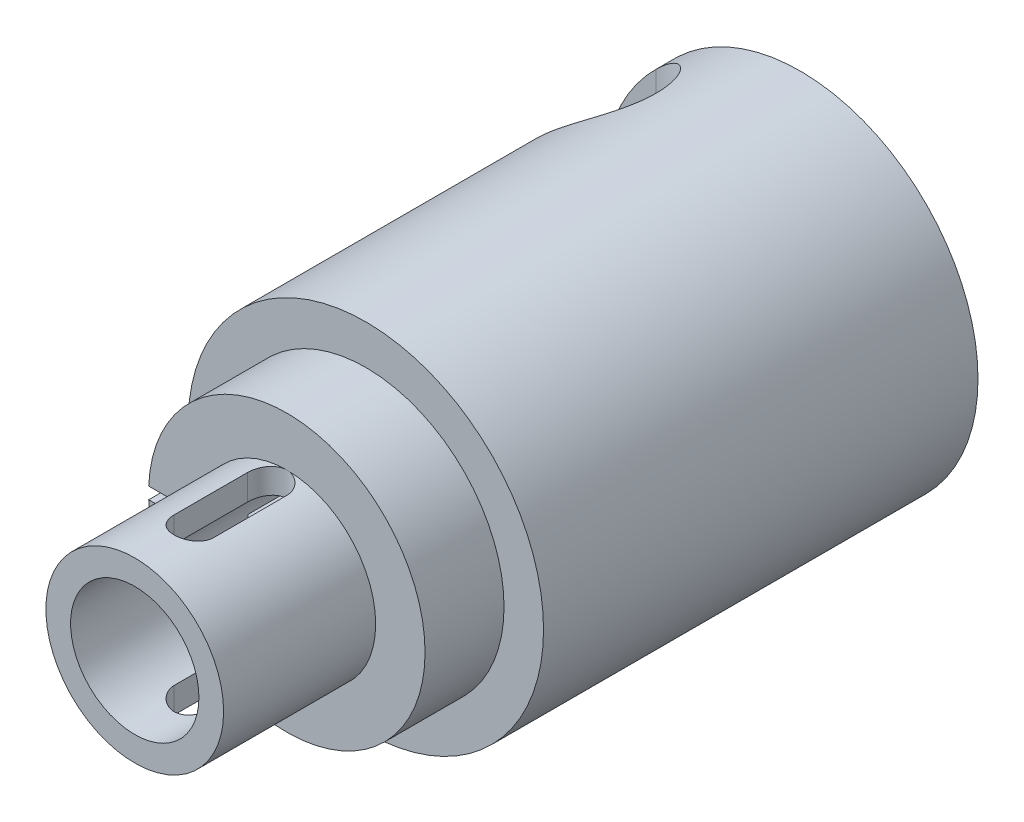
SolidWorks part; units mm, degrees
ref_plane "Спереди" through (0, 0, 0) normal (0, 0, 1) x (1, 0, 0)
ref_plane "Сверху" through (0, 0, 0) normal (0, 1, 0) x (1, 0, 0)
ref_plane "Справа" through (0, 0, 0) normal (1, 0, 0) x (0, 0, -1)
sketch "Эскиз1" plane through (0, 0, 0) normal (0, 0, 1) x (1, 0, 0)
  circle A0 centre (0, 0) radius 4.5
  dimension "D1" = 9
extrude "Бобышка-Вытянуть1" add sketch "Эскиз1" along normal blind 7.7
sketch "Эскиз3" plane through (0, 0, 0) normal (0, 0, -1) x (-1, 0, 0)
  circle A0 centre (0, 0) radius 7
  dimension "D1" = 14
extrude "Бобышка-Вытянуть2" add sketch "Эскиз3" along normal blind 4
sketch "Эскиз7" plane through (0, 0, -4) normal (0, 0, -1) x (-1, 0, 0)
  circle A5 centre (0, 0) radius 9
  point P17 (0, 0)
  dimension "D3" = 18
sketch "Эскиз6" plane through (0, 0, 0) normal (0, 1, 0) x (1, 0, 0)
  line L1 (0, -4.7) -> (0, -1) construction
  line L2 (-1, -4.7) -> (-1, -1)
  line L3 (1, -4.7) -> (1, -1)
  line L4 (-4.5, 0) -> (4.5, 0) construction
  arc A1 (-1, -4.7) -> (1, -4.7) centre (0, -4.7) ccw
  arc A2 (1, -1) -> (-1, -1) centre (0, -1) ccw
  point P2 (0, -2.85)
  dimension "D1" = 2
  dimension "D2" = 4.7
  dimension "D3" = 1
extrude "Вырез-Вытянуть3" cut sketch "Эскиз6" against normal through all both and the other way through all
extrude "Бобышка-Вытянуть4" add sketch "Эскиз7" along normal blind 22
sketch "Эскиз5" plane through (0, 0, 7.7) normal (0, 0, 1) x (1, 0, 0)
  circle A0 centre (0, 0) radius 3.25
  dimension "D1" = 6.5
extrude "Вырез-Вытянуть2" cut sketch "Эскиз5" against normal blind 26
sketch "Эскиз8" plane through (0, 0, -26) normal (0, 0, -1) x (-1, 0, 0)
  circle A0 centre (0, 0) radius 4
  dimension "D1" = 8
extrude "Вырез-Вытянуть4" cut sketch "Эскиз8" against normal blind 8 contours A0
sketch "Эскиз9" plane through (0, 0, 0) normal (0, 1, 0) x (1, 0, 0)
  line L0 (9, 26) -> (-9, 26) construction
  circle A0 centre (-33, 28) radius 40
  dimension "D1" = 80
  dimension "D2" = 2
  dimension "D3" = 33
extrude "Вырез-Вытянуть5" cut sketch "Эскиз9" against normal blind 0.3 and the other way blind 0.3
ref_plane "Плоскость1" through (0, 2.5, 0) normal (0, 1, 0) x (1, 0, 0)
sketch "Эскиз10" plane through (0, 2.5, 0) normal (0, 1, 0) x (1, 0, 0)
  line L1 (9, 26) -> (-8.995, 26) construction
  line L2 (-6.3, 25) -> (-11.6517, 25)
  line L3 (-11.6517, 25) -> (-11.6517, 19)
  line L4 (-11.6517, 19) -> (-6.3, 19)
  arc A0 (-6.3, 19) -> (-6.3, 25) centre (-6.3, 22) ccw
  dimension "D1" = 6
  dimension "D2" = 6.3
  dimension "D3" = 4
extrude "Вырез-Вытянуть6" cut sketch "Эскиз10" along normal through all
sketch "Эскиз11" plane through (0, 2.5, 0) normal (0, 1, 0) x (1, 0, 0)
  circle A0 centre (-6.3, 22) radius 1.5
  dimension "D1" = 3
extrude "Вырез-Вытянуть7" cut sketch "Эскиз11" against normal up to surface (2.2 mm away) up to face at (-5.5399, 0.3, -9.7213)
sketch "Эскиз12" plane through (0, 2.5, 0) normal (0, 1, 0) x (1, 0, 0)
  circle A0 centre (-6.3, 22) radius 1.25
  dimension "D1" = 2.5
extrude "Вырез-Вытянуть8" cut sketch "Эскиз12" against normal through all
